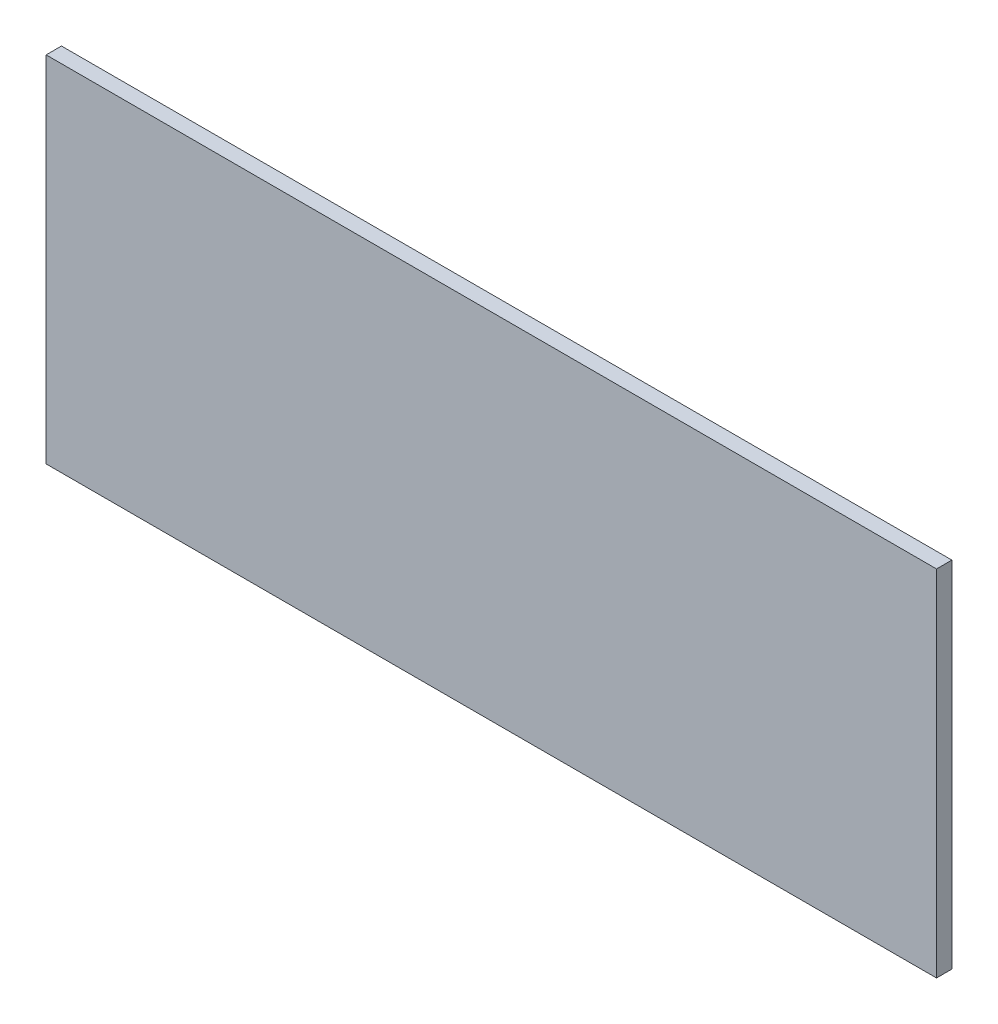
SolidWorks part; units mm, degrees
ref_plane "Plan de face" through (0, 0, 0) normal (0, 0, 1) x (1, 0, 0)
ref_plane "Plan de dessus" through (0, 0, 0) normal (0, 1, 0) x (1, 0, 0)
ref_plane "Plan de droite" through (0, 0, 0) normal (1, 0, 0) x (0, 0, -1)
sketch "Esquisse1" plane through (0, 0, 0) normal (0, 0, 1) x (1, 0, 0)
  line L1 (-191.5313, 22.8927) -> (185.4687, 22.8927)
  line L2 (-191.5313, 22.8927) -> (-191.5313, -127.1073)
  line L3 (-191.5313, -127.1073) -> (185.4687, -127.1073)
  line L4 (185.4687, 22.8927) -> (185.4687, -127.1073)
  dimension "D1" = 377
  dimension "D2" = 150
extrude "Boss.-Extru.1" add sketch "Esquisse1" along normal blind 6.5
